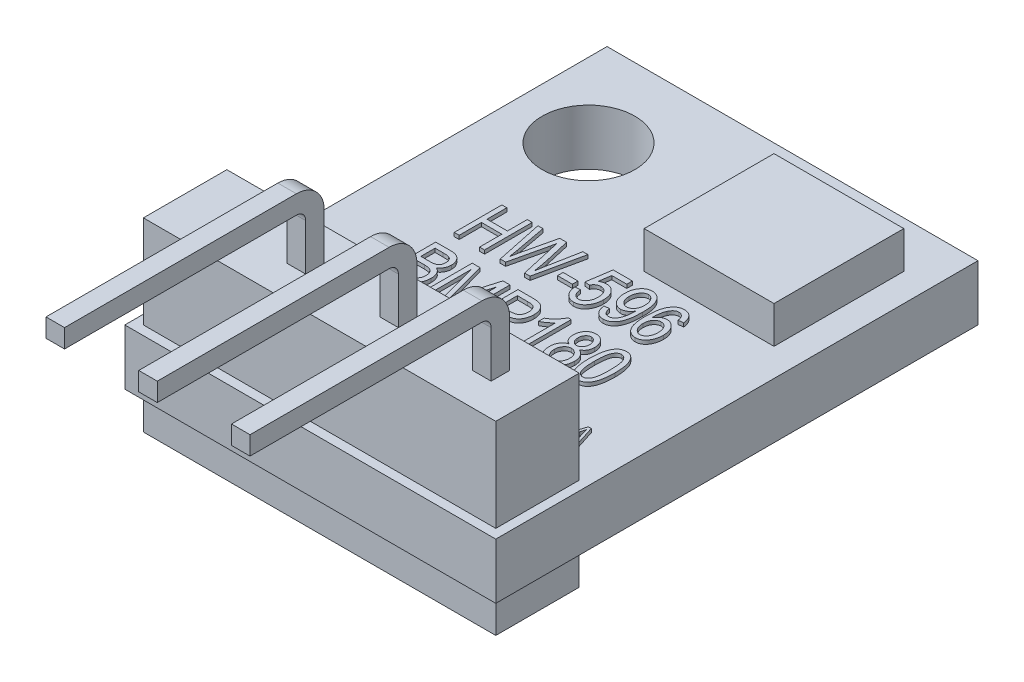
SolidWorks part; units mm, degrees
ref_plane "Front Plane" through (0, 0, 0) normal (0, 0, 1) x (1, 0, 0)
ref_plane "Top Plane" through (0, 0, 0) normal (0, 1, 0) x (1, 0, 0)
ref_plane "Right Plane" through (0, 0, 0) normal (1, 0, 0) x (0, 0, -1)
sketch "Sketch1" plane through (0, 0, 0) normal (0, 1, 0) x (1, 0, 0)
  line L0 (0, 11.625) -> (0, -1.375) construction
  line L1 (-5, 11.625) -> (5, 11.625)
  line L2 (-5, 11.625) -> (-5, -1.375)
  line L3 (-5, -1.375) -> (5, -1.375)
  line L4 (5, 11.625) -> (5, -1.375)
  line L5 (-4.75, 0) -> (4.75, 0) construction
  line L6 (-4.75, 1.125) -> (4.75, 1.125)
  line L7 (-4.75, 1.125) -> (-4.75, -1.125)
  line L8 (-4.75, -1.125) -> (4.75, -1.125)
  line L9 (4.75, 1.125) -> (4.75, -1.125)
  line L10 (2.25, 1.125) -> (2.25, -1.125) construction
  line L11 (3.5, 1.125) -> (3.5, -1.125) construction
  line L12 (0.75, 8.625) -> (4.25, 8.625) construction
  line L13 (3.25, 0.25) -> (3.75, 0.25)
  line L14 (3.25, 0.25) -> (3.25, -0.25)
  line L15 (3.25, -0.25) -> (3.75, -0.25)
  line L16 (3.75, 0.25) -> (3.75, -0.25)
  line L17 (0.75, 10.375) -> (4.25, 10.375)
  line L18 (0.75, 10.375) -> (0.75, 6.875)
  line L19 (0.75, 6.875) -> (4.25, 6.875)
  line L20 (4.25, 10.375) -> (4.25, 6.875)
  line L21 (2.5, 10.375) -> (2.5, 6.875) construction
  line L22 (-4.75, 1.625) -> (4.75, 1.625) construction
  circle A0 centre (-3, 9.125) radius 1.25
  point P20 (3.5, 0)
  point P21 (0, 0)
  point P35 (2.25, 1.625)
  point P36 (-2.25, 1.625)
  point P37 (0, 1.625)
  dimension "D8" = 2.5
  dimension "D9" = 2
  dimension "D10" = 2.5
  dimension "D1" = 10
  dimension "D2" = 13
  dimension "D3" = 2.5
  dimension "D4" = 9.5
  dimension "D5" = 2.25
  dimension "D6" = 0.5
  dimension "D7" = 1.375
  dimension "D11" = 3.5
  dimension "D12" = 3
  dimension "D13" = 2.5
  dimension "D14" = 0.5
extrude "Boss-Extrude1" add sketch "Sketch1" along normal blind 1.5 contours L4 L1 L2 L3 A0 L6 L9 L8 L7 L17 L20 L19 L18 | L9 L6 L7 L8 L13 L16 L15 L14 | L16 L13 L14 L15 region at (-0.1738, 0, -5.6393) region at (-0.0414, 0, 0) region at (3.5, 0, 0)
extrude "Boss-Extrude2" add sketch "Sketch1<3>" along normal blind 2.5 contours L20 L17 L18 L19 region at (2.5, 0, -8.625)
sketch "Sketch1<3>" plane through (0, 0, 0) normal (0, 1, 0) x (1, 0, 0) same geometry as "Sketch1"
extrude "Boss-Extrude3" add sketch "Sketch1<5>" against normal blind 1 contours L9 L6 L7 L8 L13 L16 L15 L14 | L16 L13 L14 L15 region at (-0.0414, 0, 0) region at (3.5, 0, 0)
sketch "Sketch1<5>" plane through (0, 0, 0) normal (0, 1, 0) x (1, 0, 0) same geometry as "Sketch1"
extrude "Boss-Extrude4" add sketch "Sketch1<6>" along normal blind 2.5 from vertex contours L9 L6 L7 L8 L13 L16 L15 L14 | L16 L13 L14 L15 region at (-0.0414, 0, 0) region at (3.5, 0, 0) starting at point (5, 1.5, 1.375)
sketch "Sketch1<6>" plane through (0, 0, 0) normal (0, 1, 0) x (1, 0, 0) same geometry as "Sketch1"
ref_plane "Plane1" through (3.5, 0, 0) normal (1, 0, 0) x (0, 0, -1)
sketch "Sketch2" plane through (3.5, 0, 0) normal (1, 0, 0) x (0, 0, -1)
  line L0 (0, 0) -> (0, 5.25)
  line L1 (-0.5, 5.75) -> (-6.75, 5.75)
  arc A0 (0, 5.25) -> (-0.5, 5.75) centre (-0.5, 5.25) ccw
  point P6 (0, 5.75)
  dimension "D3" = 0.5
  dimension "D1" = 5.75
  dimension "D2" = 6.75
sweep "Sweep1" add profiles "Sketch1<7>" path "Sketch2"
sketch "Sketch1<7>" plane through (0, 0, 0) normal (0, 1, 0) x (1, 0, 0) same geometry as "Sketch1"
pattern_linear "LPattern1" count 3 spacing 2.5 along (-1, 0, 0) of "Sweep1"
sketch "Sketch3" plane through (0, 0, 0) normal (0, 1, 0) x (1, 0, 0)
  line L0 (-5, 5.125) -> (5, 5.125) construction
  line L1 (-5, 11.625) -> (-5, -1.375) construction
  line L2 (5, 11.625) -> (5, -1.375) construction
  text T0 "SDA" font "Arial Narrow" height in points 3
  text T1 "SCL" font "Arial Narrow" height in points 3
  text T2 "GND" font "Arial Narrow" height in points 3
  text T3 "VIN" font "Arial Narrow" height in points 3
  text T4 "HW-596" font "Arial Narrow" height in points 5
  text T5 "BMP180" font "Arial Narrow" height in points 5
extrude "Boss-Extrude5" add sketch "Sketch3" along normal blind 0.1 from vertex starting at point (5, 1.5, 1.375)
equation "\"D4@Sketch1\"=\"D3@Sketch1\" * 4 - .5"
equation "\"D1@Sketch2\"= 6 - .5/2"
equation "\"D2@Sketch2\"= 7 - .5/2"
